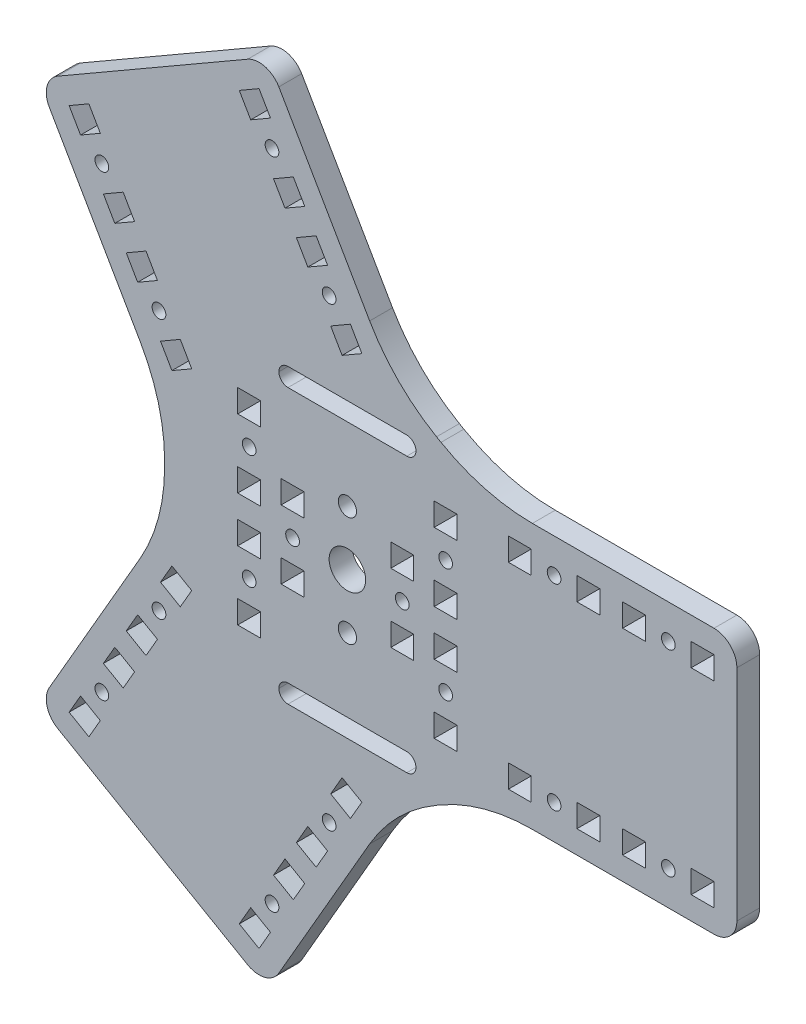
SolidWorks part; units mm, degrees
ref_plane "Plan de face" through (0, 0, 0) normal (0, 0, 1) x (1, 0, 0)
ref_plane "Plan de dessus" through (0, 0, 0) normal (0, 1, 0) x (1, 0, 0)
ref_plane "Plan de droite" through (0, 0, 0) normal (1, 0, 0) x (0, 0, -1)
sketch "Esquisse1" plane through (0, 0, 0) normal (0, 0, 1) x (1, 0, 0)
  line L0 (0, 0) -> (17.8582, 0) construction
  line L1 (-20, 40) -> (20, 40) construction
  line L2 (20, 40) -> (20, -40) construction
  line L3 (20, -40) -> (-20, -40) construction
  line L4 (-20, -40) -> (-20, 40) construction
  line L13 (0, 0) -> (0, 13.4404) construction
  line L16 (-20, -40) -> (-20, 40) construction
  line L18 (0, -40) -> (0, 40) construction
  line L19 (-15, -32) -> (-15, -28)
  line L20 (-15, 32) -> (15, 32)
  line L21 (-15, 32) -> (-15, 28)
  line L22 (-15, 28) -> (15, 28)
  line L23 (15, 32) -> (15, 28)
  line L24 (-15, -28) -> (15, -28)
  line L25 (15, -32) -> (15, -28)
  line L26 (-15, -32) -> (15, -32)
  line L42 (-15, 40) -> (15, 40) construction
  line L43 (-15, 40) -> (-15, 36) construction
  line L44 (-15, 36) -> (15, 36) construction
  line L45 (15, 40) -> (15, 36) construction
  line L46 (-15, -40) -> (-15, -36) construction
  line L47 (-15, -40) -> (15, -40) construction
  line L48 (15, -40) -> (15, -36) construction
  line L49 (-15, -36) -> (15, -36) construction
  line L57 (29.7705, 29) -> (85.235, 29)
  line L58 (85.235, 29) -> (85.235, -29)
  line L60 (85.235, -29) -> (29.7705, -29)
  line L62 (29.7705, -29) -> (20, -34.641)
  line L63 (29.7705, 29) -> (20, 34.641)
  line L64 (-40, -11.282) -> (-40, 0)
  line L65 (-67.7323, -59.3157) -> (-40, -11.282)
  line L66 (-17.5028, -88.3157) -> (-67.7323, -59.3157)
  line L67 (10.2295, -40.282) -> (-17.5028, -88.3157)
  line L68 (10.2295, -40.282) -> (20, -34.641)
  line L69 (10.2295, 40.282) -> (20, 34.641)
  line L70 (-17.5028, 88.3157) -> (10.2295, 40.282)
  line L71 (-67.7323, 59.3157) -> (-17.5028, 88.3157)
  line L72 (-40, 11.282) -> (-67.7323, 59.3157)
  line L73 (-40, 11.282) -> (-40, 0)
  circle A1 centre (0, 0) radius 4
  circle A2 centre (12, 0) radius 2 construction
  circle A3 centre (0, -12) radius 2
  circle A4 centre (-12, 0) radius 2 construction
  circle A5 centre (0, 12) radius 2
  point P12 (0, 0)
  point P19 (0, 0)
  point P21 (-28.8675, -50)
  point P24 (57.735, 0)
  point P27 (-28.8675, 50)
  point P42 (0, 0)
  point P56 (0, 0)
  point P64 (0, 0)
  point P67 (0, 0)
  point P134 (0, 0)
  line B0 (50.235, 24) -> (55.235, 24)
  line B1 (50.235, 24) -> (50.235, 19)
  line B2 (50.235, 19) -> (55.235, 19)
  line B3 (55.235, 24) -> (55.235, 19)
  line B4 (40.235, 24) -> (35.235, 24)
  line B5 (40.235, 24) -> (40.235, 19)
  line B6 (40.235, 19) -> (35.235, 19)
  line B7 (35.235, 24) -> (35.235, 19)
  circle B8 centre (45.235, 21.5) radius 1.5
  line B9 (65.235, 24) -> (60.235, 24)
  line B10 (65.235, 24) -> (65.235, 19)
  line B11 (65.235, 19) -> (60.235, 19)
  line B12 (60.235, 24) -> (60.235, 19)
  line B13 (75.235, 24) -> (80.235, 24)
  line B14 (75.235, 24) -> (75.235, 19)
  line B15 (75.235, 19) -> (80.235, 19)
  line B16 (80.235, 24) -> (80.235, 19)
  circle B17 centre (70.235, 21.5) radius 1.5
  line B18 (65.235, -24) -> (60.235, -24)
  line B19 (65.235, -24) -> (65.235, -19)
  line B20 (65.235, -19) -> (60.235, -19)
  line B21 (60.235, -24) -> (60.235, -19)
  line B22 (75.235, -24) -> (80.235, -24)
  line B23 (75.235, -24) -> (75.235, -19)
  line B24 (75.235, -19) -> (80.235, -19)
  line B25 (80.235, -24) -> (80.235, -19)
  circle B26 centre (70.235, -21.5) radius 1.5
  line B27 (50.235, -24) -> (55.235, -24)
  line B28 (50.235, -24) -> (50.235, -19)
  line B29 (50.235, -19) -> (55.235, -19)
  line B30 (55.235, -24) -> (55.235, -19)
  line B31 (40.235, -24) -> (35.235, -24)
  line B32 (40.235, -24) -> (40.235, -19)
  line B33 (40.235, -19) -> (35.235, -19)
  line B34 (35.235, -24) -> (35.235, -19)
  line B35 (45.235, -21.5) -> (45.235, -27.7802) construction
  circle B36 centre (45.235, -21.5) radius 1.5
  line B37 (80.235, -24) -> (80.235, 24) construction
  line B38 (35.235, -24) -> (35.235, 24) construction
  line B39 (35.235, 0) -> (80.235, 0) construction
  line B40 (-4.3329, -55.5048) -> (-6.8329, -59.8349)
  line B41 (-4.3329, -55.5048) -> (-8.663, -53.0048)
  line B42 (-8.663, -53.0048) -> (-11.163, -57.3349)
  line B43 (-6.8329, -59.8349) -> (-11.163, -57.3349)
  line B44 (0.6671, -46.8446) -> (3.1671, -42.5144)
  line B45 (0.6671, -46.8446) -> (-3.663, -44.3446)
  line B46 (-3.663, -44.3446) -> (-1.163, -40.0144)
  line B47 (3.1671, -42.5144) -> (-1.163, -40.0144)
  circle B48 centre (-3.998, -49.9247) radius 1.5
  line B49 (-11.8329, -68.4952) -> (-9.3329, -64.1651)
  line B50 (-11.8329, -68.4952) -> (-16.163, -65.9952)
  line B51 (-16.163, -65.9952) -> (-13.663, -61.6651)
  line B52 (-9.3329, -64.1651) -> (-13.663, -61.6651)
  line B53 (-16.8329, -77.1554) -> (-19.3329, -81.4856)
  line B54 (-16.8329, -77.1554) -> (-21.163, -74.6554)
  line B55 (-21.163, -74.6554) -> (-23.663, -78.9856)
  line B56 (-19.3329, -81.4856) -> (-23.663, -78.9856)
  circle B57 centre (-16.498, -71.5753) radius 1.5
  line B58 (-53.4021, -44.4952) -> (-50.9021, -40.1651)
  line B59 (-53.4021, -44.4952) -> (-49.072, -46.9952)
  line B60 (-49.072, -46.9952) -> (-46.572, -42.6651)
  line B61 (-50.9021, -40.1651) -> (-46.572, -42.6651)
  line B62 (-58.4021, -53.1554) -> (-60.9021, -57.4856)
  line B63 (-58.4021, -53.1554) -> (-54.072, -55.6554)
  line B64 (-54.072, -55.6554) -> (-56.572, -59.9856)
  line B65 (-60.9021, -57.4856) -> (-56.572, -59.9856)
  circle B66 centre (-53.7371, -50.0753) radius 1.5
  line B67 (-45.9021, -31.5048) -> (-48.4021, -35.8349)
  line B68 (-45.9021, -31.5048) -> (-41.572, -34.0048)
  line B69 (-41.572, -34.0048) -> (-44.072, -38.3349)
  line B70 (-48.4021, -35.8349) -> (-44.072, -38.3349)
  line B71 (-40.9021, -22.8446) -> (-38.4021, -18.5144)
  line B72 (-40.9021, -22.8446) -> (-36.572, -25.3446)
  line B73 (-36.572, -25.3446) -> (-34.072, -21.0144)
  line B74 (-38.4021, -18.5144) -> (-34.072, -21.0144)
  circle B75 centre (-41.2371, -28.4247) radius 1.5
  line B76 (-17.6175, -30.5144) -> (-40.1175, -69.4856) construction
  line B77 (-45.9021, 31.5048) -> (-48.4021, 35.8349)
  line B78 (-45.9021, 31.5048) -> (-41.572, 34.0048)
  line B79 (-41.572, 34.0048) -> (-44.072, 38.3349)
  line B80 (-48.4021, 35.8349) -> (-44.072, 38.3349)
  line B81 (-40.9021, 22.8446) -> (-38.4021, 18.5144)
  line B82 (-40.9021, 22.8446) -> (-36.572, 25.3446)
  line B83 (-36.572, 25.3446) -> (-34.072, 21.0144)
  line B84 (-38.4021, 18.5144) -> (-34.072, 21.0144)
  circle B85 centre (-41.2371, 28.4247) radius 1.5
  line B86 (-53.4021, 44.4952) -> (-50.9021, 40.1651)
  line B87 (-53.4021, 44.4952) -> (-49.072, 46.9952)
  line B88 (-49.072, 46.9952) -> (-46.572, 42.6651)
  line B89 (-50.9021, 40.1651) -> (-46.572, 42.6651)
  line B90 (-58.4021, 53.1554) -> (-60.9021, 57.4856)
  line B91 (-58.4021, 53.1554) -> (-54.072, 55.6554)
  line B92 (-54.072, 55.6554) -> (-56.572, 59.9856)
  line B93 (-60.9021, 57.4856) -> (-56.572, 59.9856)
  circle B94 centre (-53.7371, 50.0753) radius 1.5
  line B95 (-11.8329, 68.4952) -> (-9.3329, 64.1651)
  line B96 (-11.8329, 68.4952) -> (-16.163, 65.9952)
  line B97 (-16.163, 65.9952) -> (-13.663, 61.6651)
  line B98 (-9.3329, 64.1651) -> (-13.663, 61.6651)
  line B99 (-16.8329, 77.1554) -> (-19.3329, 81.4856)
  line B100 (-16.8329, 77.1554) -> (-21.163, 74.6554)
  line B101 (-21.163, 74.6554) -> (-23.663, 78.9856)
  line B102 (-19.3329, 81.4856) -> (-23.663, 78.9856)
  circle B103 centre (-16.498, 71.5753) radius 1.5
  line B104 (-4.3329, 55.5048) -> (-6.8329, 59.8349)
  line B105 (-4.3329, 55.5048) -> (-8.663, 53.0048)
  line B106 (-8.663, 53.0048) -> (-11.163, 57.3349)
  line B107 (-6.8329, 59.8349) -> (-11.163, 57.3349)
  line B108 (0.6671, 46.8446) -> (3.1671, 42.5144)
  line B109 (0.6671, 46.8446) -> (-3.663, 44.3446)
  line B110 (-3.663, 44.3446) -> (-1.163, 40.0144)
  line B111 (3.1671, 42.5144) -> (-1.163, 40.0144)
  circle B112 centre (-3.998, 49.9247) radius 1.5
  line B113 (-24, -7.5) -> (-24, -2.5)
  line B114 (-24, -7.5) -> (-19, -7.5)
  line B115 (-19, -7.5) -> (-19, -2.5)
  line B116 (-24, -2.5) -> (-19, -2.5)
  line B117 (-24, -17.5) -> (-24, -22.5)
  line B118 (-24, -17.5) -> (-19, -17.5)
  line B119 (-19, -17.5) -> (-19, -22.5)
  line B120 (-24, -22.5) -> (-19, -22.5)
  circle B121 centre (-21.5, -12.5) radius 1.5
  line B122 (-24, 7.5) -> (-24, 2.5)
  line B123 (-24, 7.5) -> (-19, 7.5)
  line B124 (-19, 7.5) -> (-19, 2.5)
  line B125 (-24, 2.5) -> (-19, 2.5)
  line B126 (-24, 17.5) -> (-24, 22.5)
  line B127 (-24, 17.5) -> (-19, 17.5)
  line B128 (-19, 17.5) -> (-19, 22.5)
  line B129 (-24, 22.5) -> (-19, 22.5)
  circle B130 centre (-21.5, 12.5) radius 1.5
  line B131 (24, 7.5) -> (24, 2.5)
  line B132 (24, 7.5) -> (19, 7.5)
  line B133 (19, 7.5) -> (19, 2.5)
  line B134 (24, 2.5) -> (19, 2.5)
  line B135 (24, 17.5) -> (24, 22.5)
  line B136 (24, 17.5) -> (19, 17.5)
  line B137 (19, 17.5) -> (19, 22.5)
  line B138 (24, 22.5) -> (19, 22.5)
  circle B139 centre (21.5, 12.5) radius 1.5
  line B140 (24, -7.5) -> (24, -2.5)
  line B141 (24, -7.5) -> (19, -7.5)
  line B142 (19, -7.5) -> (19, -2.5)
  line B143 (24, -2.5) -> (19, -2.5)
  line B144 (24, -17.5) -> (24, -22.5)
  line B145 (24, -17.5) -> (19, -17.5)
  line B146 (19, -17.5) -> (19, -22.5)
  line B147 (24, -22.5) -> (19, -22.5)
  circle B148 centre (21.5, -12.5) radius 1.5
  line B149 (24, 22.5) -> (-24, 22.5) construction
  line B150 (24, -22.5) -> (-24, -22.5) construction
  line B151 (0, -22.5) -> (0, 22.5) construction
  line B152 (14.5, -5) -> (14.5, -10)
  line B153 (14.5, -5) -> (9.5, -5)
  line B154 (9.5, -5) -> (9.5, -10)
  line B155 (14.5, -10) -> (9.5, -10)
  line B156 (14.5, 5) -> (14.5, 10)
  line B157 (14.5, 5) -> (9.5, 5)
  line B158 (9.5, 5) -> (9.5, 10)
  line B159 (14.5, 10) -> (9.5, 10)
  line B160 (12, 0) -> (18.2802, 0) construction
  circle B161 centre (12, 0) radius 1.5
  line B162 (-12, -5) -> (-12, 5) construction
  line B163 (-9.5, -5) -> (-9.5, -10)
  line B164 (-9.5, -5) -> (-14.5, -5)
  line B165 (-14.5, -5) -> (-14.5, -10)
  line B166 (-9.5, -10) -> (-14.5, -10)
  line B167 (-9.5, 5) -> (-9.5, 10)
  line B168 (-9.5, 5) -> (-14.5, 5)
  line B169 (-14.5, 5) -> (-14.5, 10)
  line B170 (-9.5, 10) -> (-14.5, 10)
  line B171 (-12, 0) -> (-5.7198, 0) construction
  circle B172 centre (-12, 0) radius 1.5
  dimension "D9" = 5
  dimension "D14" = 100
  dimension "D17" = 8
  dimension "D18" = 4
  dimension "D4" = 3
  dimension "D5" = 5
  dimension "D6" = 5
  dimension "D7" = 5
  dimension "D8" = 20
  dimension "D10" = 5
  dimension "D11" = 4
  dimension "D12" = 40
  dimension "D3" = 3
  dimension "D16" = 28
  dimension "D19" = 12
  dimension "D20" = 4
sketch_block_instance "Bloc1-4"
sketch_block "Bloc1"
sketch_block_instance "Trou M3 plots 5mm-54"
sketch_block "Trou M3 plots 5mm" parameters "D2"=3, "D1"=5, "D3"=5, "D4"=8
sketch_block_instance "Trou M3 plots 5mm-56"
sketch_block_instance "Trou M3 plots 5mm-55"
sketch_block_instance "Trou M3 plots 5mm-52"
sketch_block_instance "Bloc1-5"
sketch_block_instance "Bloc1-6"
sketch_block_instance "Bloc1-10"
sketch_block_instance "Trou M3 plots 5mm-61"
sketch_block_instance "Trou M3 plots 5mm-62"
extrude "Boss.-Extru.1" add sketch "Esquisse1" along normal blind 5
fillet "Congé1" radius 2 8 edges at (-15, -32, 2.5) (-15, -28, 2.5) (15, -28, 2.5) (15, -32, 2.5) (15, 28, 2.5) (15, 32, 2.5) (-15, 28, 2.5) (-15, 32, 2.5)
fillet "Congé2" radius 5 6 edges at (-17.5028, -88.3157, 2.5) (-67.7323, -59.3157, 2.5) (85.235, -29, 2.5) (-67.7323, 59.3157, 2.5) (85.235, 29, 2.5) (-17.5028, 88.3157, 2.5)
fillet "Congé3" radius 40 6 edges at (-40, 11.282, 2.5) (-40, -11.282, 2.5) (10.2295, -40.282, 2.5) (29.7705, -29, 2.5) (29.7705, 29, 2.5) (10.2295, 40.282, 2.5)
